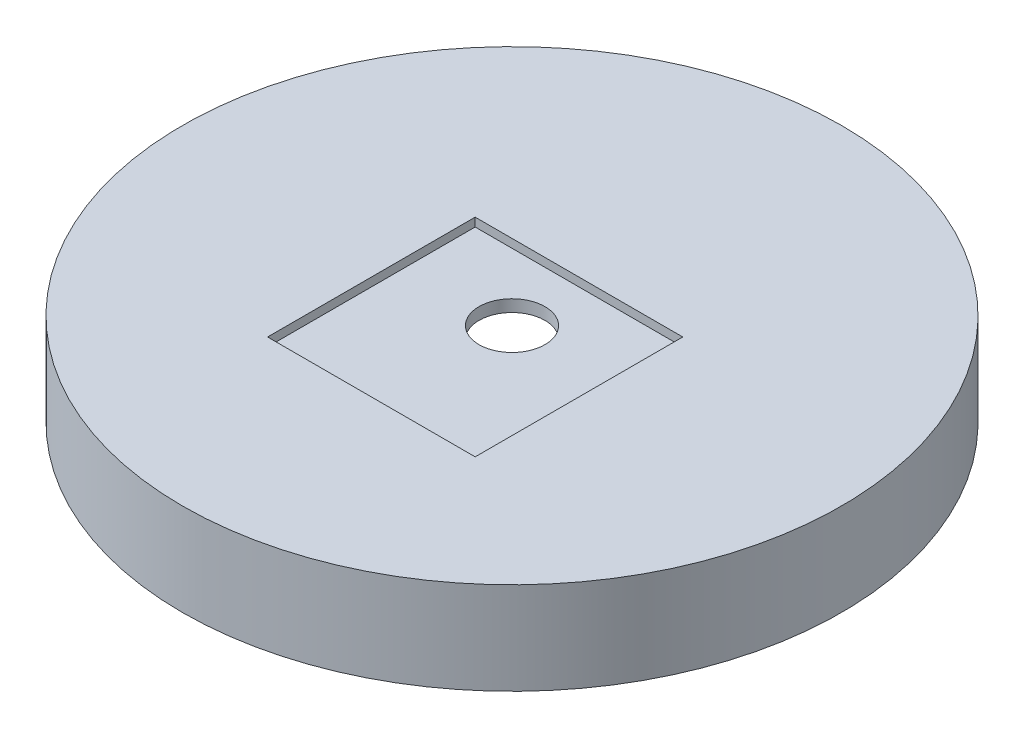
SolidWorks part; units mm, degrees
ref_plane "Front Plane" through (0, 0, 0) normal (0, 0, 1) x (1, 0, 0)
ref_plane "Top Plane" through (0, 0, 0) normal (0, 1, 0) x (1, 0, 0)
ref_plane "Right Plane" through (0, 0, 0) normal (1, 0, 0) x (0, 0, -1)
sketch "Sketch3" plane through (0, 0, 0) normal (0, 0, 1) x (1, 0, 0)
  line L0 (0, 0) -> (21, 0) construction
  line L1 (0, 6.35) -> (21, 6.35) construction
  line L2 (21, 0) -> (2.5, 5.4429)
  line L3 (2.5, -13.9932) -> (2.5, 1.2597) construction
  line L4 (0, 0) -> (0, -13.9932) construction
  line L5 (21, 0) -> (25, 0)
  line L6 (2.5, 7) -> (2.5, 5.4429)
  line L9 (25, 7) -> (25, 0)
  line L11 (25, 7) -> (2.5, 7)
  line L12 (2.5, 5.4429) -> (2.5, 7) construction
  dimension "D1" = 21
  dimension "D2" = 7
  dimension "D3" = 2.5
  dimension "D4" = 4
  dimension "D5" = 5.4429
revolve "Revolve1" add sketch "Sketch3" angle 360 about L4
sketch "Sketch for side slot DNU" plane through (0, 0, 0) normal (0, 0, 1) x (1, 0, 0)
  line L0 (0, 0) -> (0, 18.8028) construction
  line L1 (0, 0) -> (-24.5114, 0) construction
  line L2 (-7.874, 8.382) -> (7.874, 8.382)
  line L3 (-7.874, 8.382) -> (-7.874, 9.398)
  line L4 (-7.874, 9.398) -> (7.874, 9.398)
  line L5 (7.874, 8.382) -> (7.874, 9.398)
  line L6 (-7.874, 8.382) -> (7.874, 9.398) construction
  line L7 (-7.874, 9.398) -> (7.874, 8.382) construction
  point P3 (0, 8.89)
  dimension "D1" = 15.748
  dimension "D2" = 1.016
  dimension "D3" = 8.89
ref_plane "Plane4" through (0, 12.7, 0) normal (0, 1, 0) x (1, 0, 0)
sketch "Sketch5" plane through (0, 12.7, 0) normal (0, 1, 0) x (1, 0, 0)
  line L0 (0, 0) -> (35.335, 0) construction
  line L1 (0, 0) -> (0, 26.2568) construction
  line L2 (7.874, 5.08) -> (-7.874, 5.08)
  line L3 (-7.874, 5.08) -> (-7.874, -10.668)
  line L4 (-7.874, -10.668) -> (7.874, -10.668)
  line L5 (7.874, -10.668) -> (7.874, 5.08)
  point P7 (0, 5.08)
  dimension "D1" = 15.748
  dimension "D2" = 15.748
  dimension "D3" = 5.08
extrude "Cut-Extrude1" cut sketch "Sketch5" against normal blind 6.35
